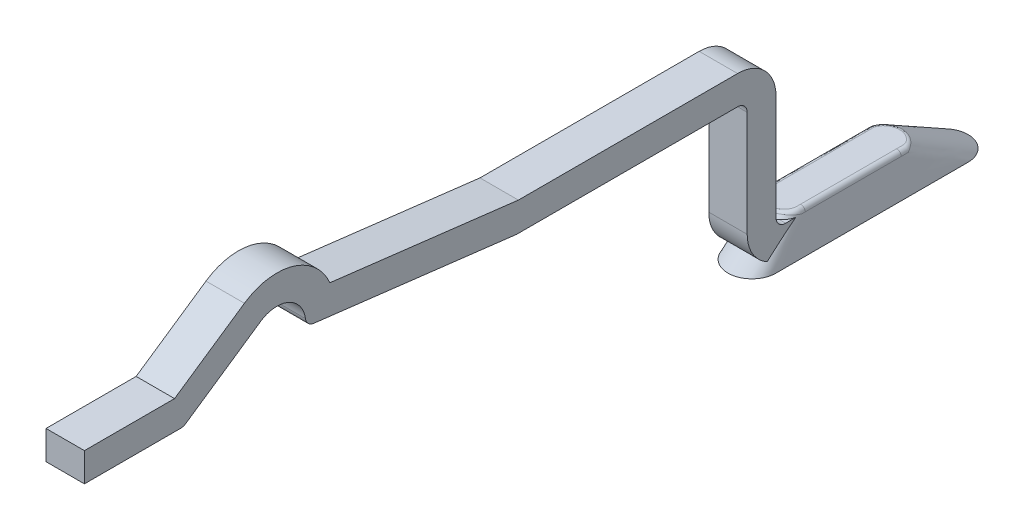
SolidWorks part; units mm, degrees
material "Pure Gold"
ref_plane "Front Plane" through (0, 0, 0) normal (0, 0, 1) x (1, 0, 0)
ref_plane "Top Plane" through (0, 0, 0) normal (0, 1, 0) x (1, 0, 0)
ref_plane "Right Plane" through (0, 0, 0) normal (1, 0, 0) x (0, 0, -1)
ref_plane "Plane1" through (0, -0.05, 0) normal (0, 1, 0) x (1, 0, 0)
sketch "Sketch1" plane through (0, 0, 0) normal (1, 0, 0) x (0, 0, -1)
  line L0 (1.5, 0) -> (0.4, 0)
  line L1 (0.2811, 0) -> (-0.2811, 0) construction
  line L2 (0, 0.4) -> (0, 1.5)
  line L3 (0, 0.2811) -> (0, -0.2811) construction
  line L4 (-0.1, 1.6) -> (-2.4, 1.6)
  line L5 (-2.4, 1.6) -> (-4.5119, 1.8538)
  line L6 (-5.0654, 2.1479) -> (-5.8437, 1.6174)
  line L7 (-5.9, 1.6) -> (-6.9, 1.6)
  arc A0 (0.4, 0) -> (0, 0.4) centre (0.4, 0.4) cw
  arc A1 (0, 1.5) -> (-0.1, 1.6) centre (-0.1, 1.5) ccw
  arc A2 (-4.5991, 1.9398) -> (-5.0654, 2.1479) centre (-4.8965, 1.9) ccw
  arc A3 (-4.5119, 1.8538) -> (-4.5991, 1.9398) centre (-4.5, 1.9531) cw
  arc A4 (-5.8437, 1.6174) -> (-5.9, 1.6) centre (-5.9, 1.7) cw
  point P11 (0, 0)
  point P14 (0, 1.6)
  dimension "D3" = 0.4
  dimension "D4" = 0.1
  dimension "D6" = 0.1
  dimension "D7" = 0.1
  dimension "D9" = 0.3
  dimension "D1" = 1.6
  dimension "D2" = 1.5
  dimension "D5" = 2.4
  dimension "D8" = 5.9
  dimension "D10" = 1
  dimension "D11" = 4.5
  dimension "D12" = 0
  dimension "D13" = 0.3
extrude "Extrude-Thin1" add sketch "Sketch1" along normal mid plane 0.4 thin thin type one direction wall 0.3
sketch "Sketch2" plane through (0, -0.05, 0) normal (0, 1, 0) x (1, 0, 0)
  line L0 (0, 2.25) -> (0, 0.25) construction
  line L1 (0, -1.7919) -> (0, 1.7919) construction
  line L2 (0.25, 2.25) -> (0.25, 0.25)
  line L3 (-0.25, 2.25) -> (-0.25, 0.25)
  line L4 (-0.2811, 0) -> (0.2811, 0) construction
  arc A0 (0.25, 2.25) -> (-0.25, 2.25) centre (0, 2.25) ccw
  arc A1 (-0.25, 0.25) -> (0.25, 0.25) centre (0, 0.25) ccw
  point P5 (0, 1.25)
  dimension "D1" = 0.5
  dimension "D2" = 1.25
  dimension "D3" = 2
ref_plane "Plane2" through (0, 0.35, 0) normal (0, 1, 0) x (1, 0, 0)
sketch "Sketch3" plane through (0, 0.35, 0) normal (0, 1, 0) x (1, 0, 0)
  line L0 (0, 1.6) -> (0, 0.6) construction
  line L1 (0, 2.25) -> (0, 0.25) construction
  line L2 (0.2, 1.6) -> (0.2, 0.6)
  line L3 (-0.2, 1.6) -> (-0.2, 0.6)
  line L4 (-0.2811, 0) -> (0.2811, 0) construction
  arc A0 (0.2, 1.6) -> (-0.2, 1.6) centre (0, 1.6) ccw
  arc A1 (-0.2, 0.6) -> (0.2, 0.6) centre (0, 0.6) ccw
  point P4 (0, 1.1)
  dimension "D2" = 0.2
  dimension "D1" = 1
  dimension "D3" = 1.1
loft "Loft1" add profiles "Sketch3", "Sketch2"
fillet "Fillet2" radius 0.05 4 edges
